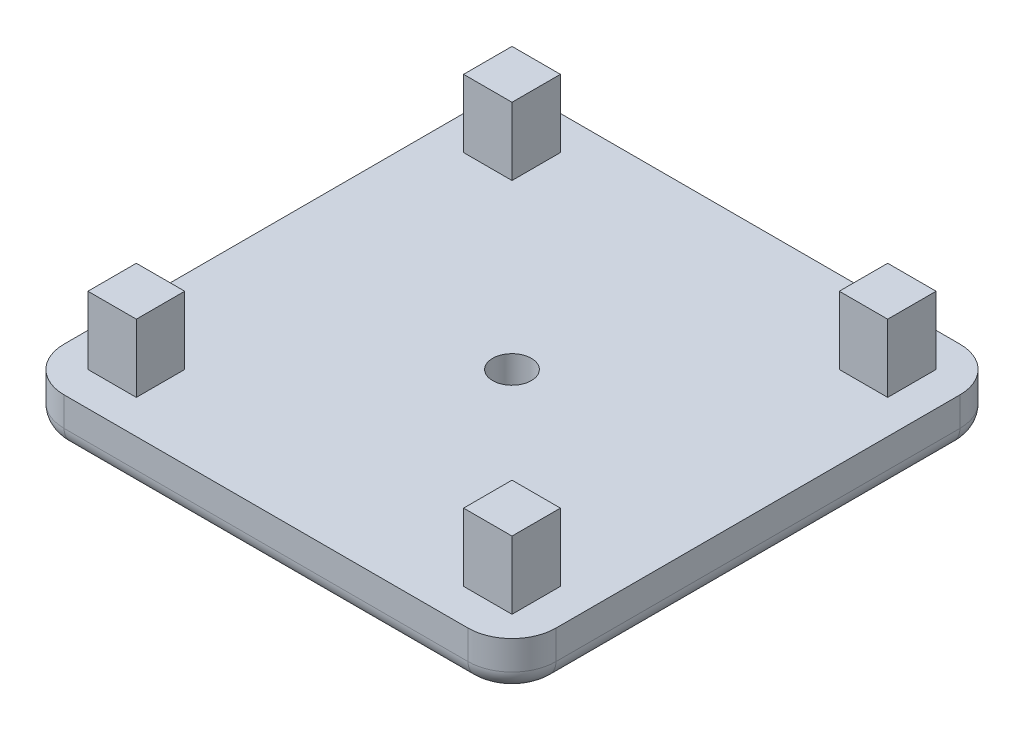
SolidWorks part; units mm, degrees
ref_plane "Front Plane" through (0, 0, 0) normal (0, 0, 1) x (1, 0, 0)
ref_plane "Top Plane" through (0, 0, 0) normal (0, 1, 0) x (1, 0, 0)
ref_plane "Right Plane" through (0, 0, 0) normal (1, 0, 0) x (0, 0, -1)
sketch "Sketch1" plane through (0, 0, 0) normal (0, 1, 0) x (1, 0, 0)
  line L0 (0, 40.9558) -> (0, -31.5279) construction
  line L1 (-25.4, 25.4) -> (25.4, 25.4)
  line L2 (-25.4, 25.4) -> (-25.4, -25.4)
  line L3 (-25.4, -25.4) -> (25.4, -25.4)
  line L4 (25.4, 25.4) -> (25.4, -25.4)
  line L5 (-25.4, 25.4) -> (25.4, -25.4) construction
  line L6 (-25.4, -25.4) -> (25.4, 25.4) construction
  line L7 (-16.9, 16.9) -> (-21.9, 16.9)
  line L8 (-16.9, 16.9) -> (-16.9, 21.9)
  line L9 (-16.9, 21.9) -> (-21.9, 21.9)
  line L10 (-21.9, 16.9) -> (-21.9, 21.9)
  line L11 (-16.9, 16.9) -> (-21.9, 21.9) construction
  line L12 (-16.9, 21.9) -> (-21.9, 16.9) construction
  line L13 (39.9537, 0) -> (-38.7868, 0) construction
  line L14 (16.9, 16.9) -> (21.9, 16.9)
  line L15 (16.9, 21.9) -> (21.9, 16.9) construction
  line L16 (16.9, 16.9) -> (21.9, 21.9) construction
  line L17 (25.4, 25.4) -> (-25.4, -25.4) construction
  line L18 (21.9, 16.9) -> (21.9, 21.9)
  line L19 (16.9, 21.9) -> (21.9, 21.9)
  line L20 (16.9, 16.9) -> (16.9, 21.9)
  line L21 (-21.9, -16.9) -> (-21.9, -21.9)
  line L22 (16.9, -21.9) -> (21.9, -21.9)
  line L23 (-16.9, -21.9) -> (-21.9, -21.9)
  line L24 (25.4, -25.4) -> (-25.4, 25.4) construction
  line L25 (16.9, -16.9) -> (21.9, -21.9) construction
  line L26 (16.9, -21.9) -> (21.9, -16.9) construction
  line L27 (-16.9, -21.9) -> (-21.9, -16.9) construction
  line L28 (-16.9, -16.9) -> (-21.9, -21.9) construction
  line L29 (-25.4, 25.4) -> (25.4, -25.4) construction
  line L30 (-25.4, -25.4) -> (25.4, 25.4) construction
  line L31 (0, -40.9558) -> (0, 31.5279) construction
  line L32 (16.9, -16.9) -> (16.9, -21.9)
  line L33 (21.9, -16.9) -> (21.9, -21.9)
  line L34 (16.9, -16.9) -> (21.9, -16.9)
  line L35 (-16.9, -16.9) -> (-16.9, -21.9)
  line L36 (-16.9, -16.9) -> (-21.9, -16.9)
  circle A0 centre (0, 0) radius 2
  point P0 (0, 0)
  point P8 (-19.4, 19.4)
  point P21 (19.4, 19.4)
  point P32 (19.4, -19.4)
  point P33 (-19.4, -19.4)
  dimension "D3" = 4
  dimension "D1" = 50.8
  dimension "D2" = 50.8
  dimension "D4" = 5
  dimension "D6" = 6
extrude "Boss-Extrude1" add sketch "Sketch1" along normal blind 5
fillet "Fillet1" radius 2 4 edges at (-25.4, 0, 0) (0, 0, -25.4) (0, 0, 25.4) (25.4, 0, 0)
fillet "Fillet2" radius 4.54 8 edges at (24.8142, 0.5858, -24.8142) (24.8142, 0.5858, 24.8142) (-24.8142, 0.5858, -24.8142) (-24.8142, 0.5858, 24.8142) (-25.4, 3.5, 25.4) (-25.4, 3.5, -25.4) (25.4, 3.5, 25.4) (25.4, 3.5, -25.4)
extrude "Boss-Extrude2" add sketch "Sketch1<6>" along normal blind 12 contours L35 L36 L21 L23 | L34 L32 L22 L33 | L20 L14 L18 L19 | L8 L9 L10 L7 region at (19.4, 0, -19.4) region at (-19.4, 0, 19.4) region at (19.4, 0, 19.4)
sketch "Sketch1<6>" plane through (0, 0, 0) normal (0, 1, 0) x (1, 0, 0) same geometry as "Sketch1"
